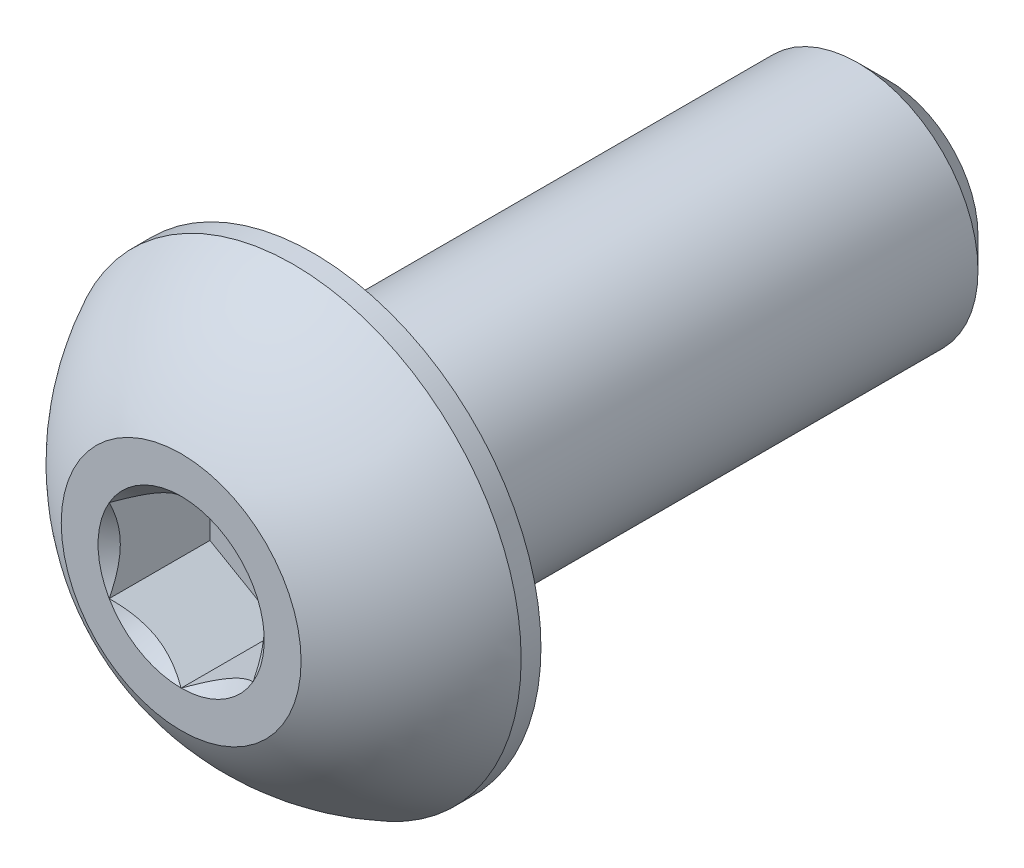
SolidWorks part; units mm, degrees
material "Plain Carbon Steel"
ref_plane "Front Plane" through (0, 0, 0) normal (0, 0, 1) x (1, 0, 0)
ref_plane "Top Plane" through (0, 0, 0) normal (0, 1, 0) x (1, 0, 0)
ref_plane "Right Plane" through (0, 0, 0) normal (1, 0, 0) x (0, 0, -1)
sketch "Sketch1" plane through (0, 0, 0) normal (1, 0, 0) x (0, 0, -1)
  line L0 (-7.375, 0) -> (7.375, 0) construction
  line L1 (-4.625, 4.75) -> (-4.625, -4.75) construction
  line L2 (7.375, 2.5) -> (7.375, -2.5) construction
  line L3 (7.325, 2.5866) -> (7.725, 1.8938) construction
  line L4 (7.725, 1.8938) -> (8.125, 2.5866) construction
  line L5 (8.125, 2.5866) -> (7.325, 2.5866) construction
  line L6 (7.375, 2.5) -> (8.075, 2.5) construction
  line L7 (7.725, 2.5866) -> (7.725, 2.5) construction
  line L8 (7.725, 2.5) -> (7.725, 1.9804) construction
  line L9 (7.725, 1.9804) -> (7.725, 1.8938) construction
  line L10 (7.675, 1.9804) -> (7.775, 1.9804)
  line L11 (7.35, 2.5433) -> (8.1, 2.5433)
  line L12 (7.775, 1.9804) -> (8.1, 2.5433)
  line L13 (7.675, 1.9804) -> (7.35, 2.5433)
  line L14 (-7.375, 1.5) -> (-7.375, -1.5) construction
  line L15 (7.375, 2.5) -> (-4.625, 2.5) construction
  point P3 (-4.625, 0)
  point P6 (-5.275, 0)
  point P21 (7.725, 2.5433)
  point P24 (-5.0375, 4.75)
  point P25 (5.375, -2.5)
  point P26 (-7.375, 2.5)
  dimension "Head Height" = 2.75
  dimension "Length" = 12
  dimension "Head Dia" = 9.5
  dimension "Thread Dia" = 5
  dimension "Pitch" = 0.8
  dimension "D2" = 0.1
  dimension "Drive Size" = 3
  dimension "D1" = 2.1
  dimension "D3" = 0.4125
  dimension "D4" = 2
sketch "Sketch2" plane through (0, 0, 0) normal (1, 0, 0) x (0, 0, -1)
  line L0 (-7.375, 0) -> (7.375, 0)
  line L1 (7.375, 0) -> (7.375, 1.86)
  line L2 (7.375, 2.5) -> (7.375, -2.5) construction
  line L3 (7.375, 1.86) -> (6.735, 2.5)
  line L4 (6.735, 2.5) -> (-4.625, 2.5)
  line L5 (-4.625, 4.75) -> (-4.625, -4.75) construction
  line L6 (-4.625, 2.5) -> (-4.625, 4.75)
  line L7 (-4.625, 4.75) -> (-5.0375, 4.75)
  line L8 (7.375, 2.5) -> (8.075, 2.5) construction
  line L9 (-7.375, 0) -> (-7.375, 2.5)
  arc A0 (-7.375, 2.5) -> (-5.0375, 4.75) centre (-2.7169, 0) cw
  dimension "D1" = 0.64
  dimension "D2" = 45
revolve "Revolve1" add sketch "Sketch2" angle 360 about L0
sketch "Sketch3" plane through (0, 0, 7.375) normal (0, 0, 1) x (1, 0, 0)
  line L1 (0, 1.7321) -> (-1.5, 0.866)
  line L2 (-1.5, 0.866) -> (-1.5, -0.866)
  line L3 (-1.5, -0.866) -> (0, -1.7321)
  line L4 (0, -1.7321) -> (1.5, -0.866)
  line L5 (1.5, -0.866) -> (1.5, 0.866)
  line L6 (1.5, 0.866) -> (0, 1.7321)
  circle A0 centre (0, 0) radius 1.5 construction
  dimension "D1" = 3
extrude "Cut-Extrude1" cut sketch "Sketch3" against normal up to vertex (2.1 mm away) up to point (0, 0, 5.275)
sketch "Sketch4" plane through (0, 0, 7.375) normal (0, 0, 1) x (1, 0, 0)
  circle A0 centre (0, 0) radius 1.7321
extrude "Cut-Extrude2" cut sketch "Sketch4" against normal blind 10 draft 45
split "Split1" [suppressed] bodies to split 106
sketch "Sketch5" [suppressed] plane through (0, 0, -7.375) normal (0, 0, -1) x (-1, 0, 0)
  circle A0 centre (0, 0) radius 2.5 construction
  circle A1 centre (0, 0) radius 2.5
curve "Helix/Spiral1" [suppressed] pitch 0.8 height 12.8 turns 16
sketch "Sketch6" [suppressed] plane through (0, 0, 0) normal (1, 0, 0) x (0, 0, -1)
  line L0 (7.675, 1.9804) -> (7.775, 1.9804) construction
  line L1 (7.675, 1.9804) -> (7.35, 2.5433) construction
  line L2 (7.35, 2.5433) -> (8.1, 2.5433) construction
  line L3 (7.775, 1.9804) -> (8.1, 2.5433) construction
  line L4 (7.675, 1.9804) -> (7.775, 1.9804)
  line L5 (7.675, 1.9804) -> (7.35, 2.5433)
  line L6 (7.35, 2.5433) -> (8.1, 2.5433)
  line L7 (7.775, 1.9804) -> (8.1, 2.5433)
sweep "Cut-Sweep1" [suppressed] cut profiles "Sketch6" path "Helix/Spiral1"
sketch "Sketch7" [suppressed] plane through (0, 0, 4.625) normal (0, 0, -1) x (-1, 0, 0)
  circle A1 centre (0, 0) radius 2.5
  circle A2 centre (0, 0) radius 2.5
  dimension "D1" = 0
extrude "Boss-Extrude1" [suppressed] add sketch "Sketch7" along normal blind 10 draft 30
equation "\"D2@Sketch1\" = \"Pitch@Sketch1\" / 8"
equation "\"D1@Sketch1\"=\"Drive Size@Sketch1\"*.7"
equation "\"D3@Sketch1\"=\"Head Height@Sketch1\"*.15"
equation "\"D1@Sketch2\"=\"Pitch@Sketch1\"*.8"
equation "\"D1@Sketch3\"=\"Drive Size@Sketch1\""
equation "\"D4@Helix/Spiral1\"=\"Pitch@Sketch1\""
equation "\"D3@Helix/Spiral1\"=\"Length@Sketch1\"+\"Pitch@Sketch1\""
equation "\"D4@Sketch1\"=\"Pitch@Sketch1\"*2.5"
